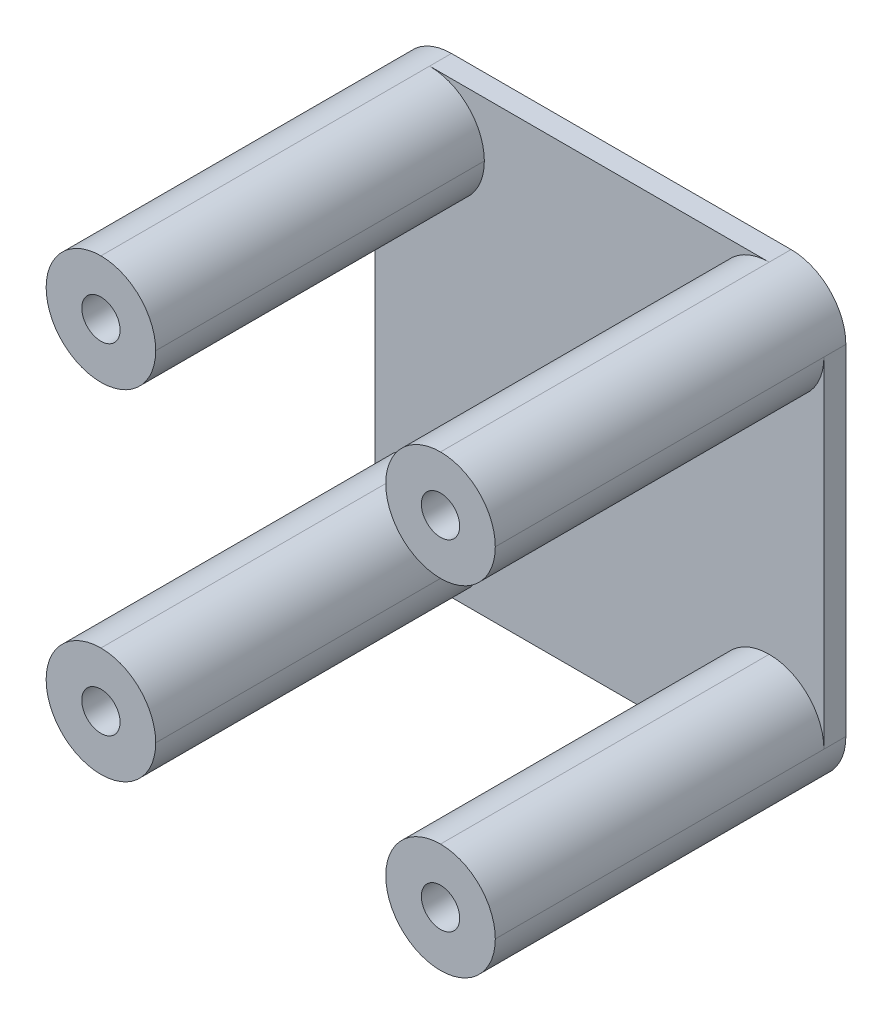
SolidWorks part; units mm, degrees
ref_plane "Front Plane" through (0, 0, 0) normal (0, 0, 1) x (1, 0, 0)
ref_plane "Top Plane" through (0, 0, 0) normal (0, 1, 0) x (1, 0, 0)
ref_plane "Right Plane" through (0, 0, 0) normal (1, 0, 0) x (0, 0, -1)
sketch "Sketch1" plane through (0, 0, 0) normal (0, 0, 1) x (1, 0, 0)
  line L0 (-55.0083, 19.8562) -> (-14.0083, 19.8562) construction
  line L1 (-55.0083, 24.8562) -> (-14.0083, 24.8562)
  line L2 (-55.0083, 24.8562) -> (-55.0083, -16.1438)
  line L3 (-55.0083, -16.1438) -> (-14.0083, -16.1438)
  line L4 (-14.0083, 24.8562) -> (-14.0083, -16.1438)
  line L5 (-50.0083, 24.8562) -> (-50.0083, -16.1438) construction
  line L6 (-55.0083, -11.1438) -> (-14.0083, -11.1438) construction
  line L7 (-19.0083, 24.8562) -> (-19.0083, -16.1438) construction
  line L8 (-55.0083, 24.8562) -> (-14.0083, -16.1438) construction
  line L9 (-55.0083, -16.1438) -> (-14.0083, 24.8562) construction
  circle A0 centre (-50.0083, 19.8562) radius 1.75
  circle A1 centre (-50.0083, -11.1438) radius 1.75
  circle A2 centre (-19.0083, -11.1438) radius 1.75
  circle A3 centre (-19.0083, 19.8562) radius 1.75
  circle A4 centre (-34.5083, 4.3562) radius 1.25
  dimension "D1" = 41
  dimension "D2" = 41
  dimension "D3" = 5
  dimension "D4" = 5
  dimension "D5" = 5
  dimension "D6" = 5
extrude "Boss-Extrude1" add sketch "Sketch1" along normal blind 2
sketch "Sketch2" plane through (0, 0, 2) normal (0, 0, 1) x (1, 0, 0)
  line L1 (-55.0083, 24.8562) -> (-45.0083, 24.8562)
  line L2 (-55.0083, 24.8562) -> (-55.0083, 14.8562)
  line L3 (-55.0083, 14.8562) -> (-45.0083, 14.8562)
  line L4 (-45.0083, 24.8562) -> (-45.0083, 14.8562)
  line L5 (-55.0083, -16.1438) -> (-45.0083, -16.1438)
  line L6 (-55.0083, -16.1438) -> (-55.0083, -6.1438)
  line L7 (-55.0083, -6.1438) -> (-45.0083, -6.1438)
  line L8 (-45.0083, -16.1438) -> (-45.0083, -6.1438)
  line L9 (-14.0083, -16.1438) -> (-24.0083, -16.1438)
  line L10 (-14.0083, -16.1438) -> (-14.0083, -6.1438)
  line L11 (-14.0083, -6.1438) -> (-24.0083, -6.1438)
  line L12 (-24.0083, -16.1438) -> (-24.0083, -6.1438)
  line L13 (-14.0083, 24.8562) -> (-24.0083, 24.8562)
  line L14 (-14.0083, 24.8562) -> (-14.0083, 14.8562)
  line L15 (-14.0083, 14.8562) -> (-24.0083, 14.8562)
  line L16 (-24.0083, 24.8562) -> (-24.0083, 14.8562)
  circle A0 centre (-50.0083, 19.8562) radius 1.75
  circle A1 centre (-50.0083, -11.1438) radius 1.75
  circle A2 centre (-19.0083, -11.1438) radius 1.75
  circle A3 centre (-19.0083, 19.8562) radius 1.75
  dimension "D1" = 10
  dimension "D2" = 10
  dimension "D3" = 10
  dimension "D4" = 10
  dimension "D5" = 10
  dimension "D6" = 10
  dimension "D7" = 10
  dimension "D8" = 10
extrude "Boss-Extrude2" add sketch "Sketch2" along normal blind 30
fillet "Fillet1" radius 5 16 edges at (-24.0083, 24.8562, 17) (-24.0083, -6.1438, 17) (-55.0083, -6.1438, 17) (-55.0083, 14.8562, 17) (-45.0083, 24.8562, 17) (-45.0083, -6.1438, 17) (-45.0083, -16.1438, 17) (-24.0083, -16.1438, 17) (-14.0083, -6.1438, 17) (-14.0083, 14.8562, 17) (-24.0083, 14.8562, 17) (-45.0083, 14.8562, 17) (-14.0083, -16.1438, 16) (-14.0083, 24.8562, 16) (-55.0083, -16.1438, 16) (-55.0083, 24.8562, 16)
